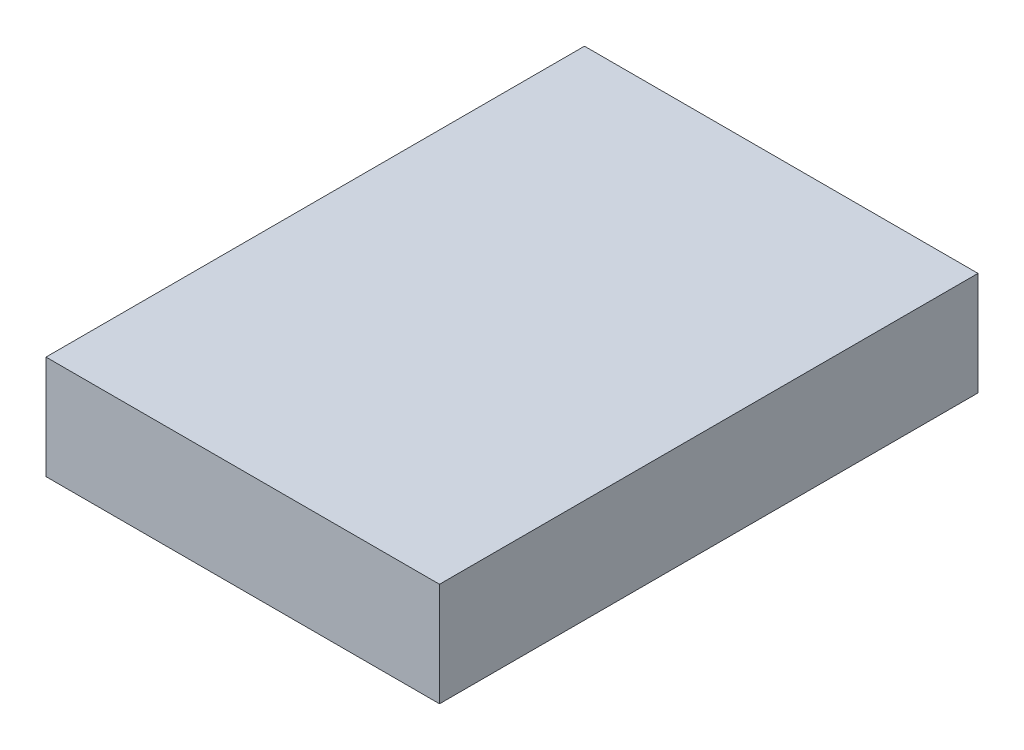
SolidWorks part; units mm, degrees
ref_plane "XY" through (0, 0, 0) normal (0, 0, 1) x (1, 0, 0)
ref_plane "XZ" through (0, 0, 0) normal (0, 1, 0) x (1, 0, 0)
ref_plane "YZ" through (0, 0, 0) normal (1, 0, 0) x (0, 0, -1)
ref_axis "X" through (-88.99, 0, 0) along (1, 0, 0)
ref_axis "Y" through (0, -55, 0) along (0, 1, 0)
ref_axis "Z" through (0, 0, 55) along (0, 0, -1)
sketch "Sketch1" plane through (0, 0, 0) normal (0, 1, 0) x (1, 0, 0)
  line L1 (-1.9, -2.6) -> (1.9, -2.6)
  line L2 (-1.9, -2.6) -> (-1.9, 2.6)
  line L3 (-1.9, 2.6) -> (1.9, 2.6)
  line L4 (1.9, -2.6) -> (1.9, 2.6)
  line L5 (-1.9, -2.6) -> (1.9, 2.6) construction
  line L6 (-1.9, 2.6) -> (1.9, -2.6) construction
  point P0 (0, 0)
  dimension "D1" = 3.8
  dimension "D2" = 5.2
extrude "Boss-Extrude1" add sketch "Sketch1" along normal blind 1
